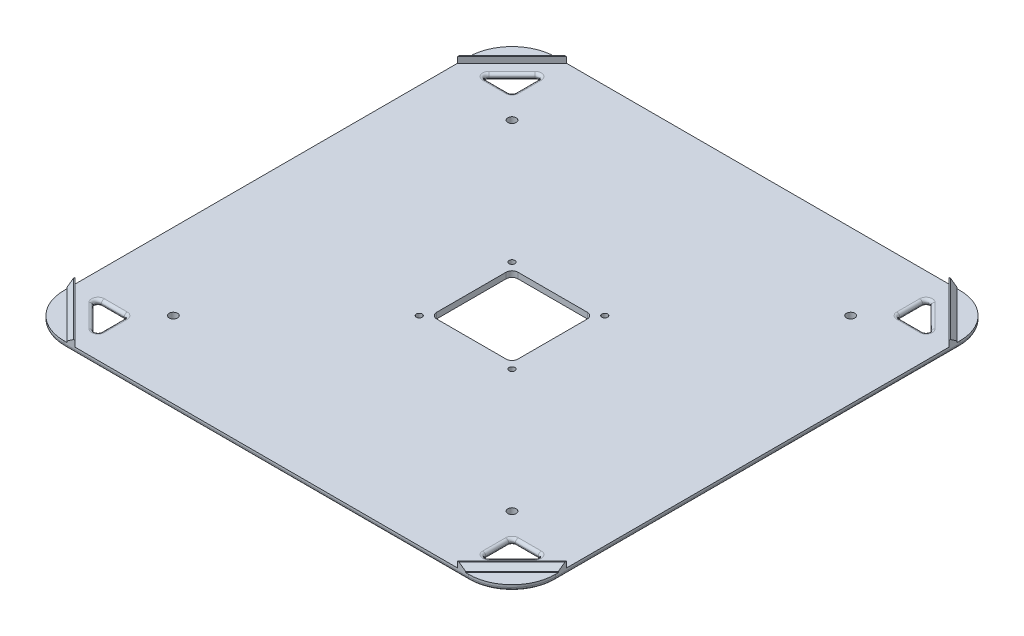
SolidWorks part; units mm, degrees
ref_plane "Front Plane" through (0, 0, 0) normal (0, 0, 1) x (1, 0, 0)
ref_plane "Top Plane" through (0, 0, 0) normal (0, 1, 0) x (1, 0, 0)
ref_plane "Right Plane" through (0, 0, 0) normal (1, 0, 0) x (0, 0, -1)
sketch "Sketch1" plane through (0, 0, 0) normal (0, 1, 0) x (1, 0, 0)
  line L5 (-134.62, -134.62) -> (134.62, -134.62)
  line L6 (-134.62, -134.62) -> (-134.62, 134.62)
  line L7 (-134.62, 134.62) -> (134.62, 134.62)
  line L8 (134.62, -134.62) -> (134.62, 134.62)
  line L9 (-134.62, -134.62) -> (134.62, 134.62) construction
  line L10 (-134.62, 134.62) -> (134.62, -134.62) construction
  point P0 (0, 0)
  dimension "D1" = 269.24
extrude "Boss-Extrude1" add sketch "Sketch1" along normal blind 3.175
fillet "Fillet1" radius 23.8125 4 edges at (134.62, 1.5875, 134.62) (134.62, 1.5875, -134.62) (-134.62, 1.5875, -134.62) (-134.62, 1.5875, 134.62)
fillet "Fillet2" radius 1.905 8 edges at (0, 0, -134.62) (127.6455, 0, -127.6455) (134.62, 0, 0) (127.6455, 0, 127.6455) (0, 0, 134.62) (-127.6455, 0, 127.6455) (-134.62, 0, 0) (-127.6455, 0, -127.6455)
sketch "Sketch9" plane through (0, 3.175, 0) normal (0, 1, 0) x (1, 0, 0)
  line L0 (134.62, -109.22) -> (109.22, -134.62)
  line L1 (109.22, -134.62) -> (104.7299, -134.62)
  line L2 (104.7299, -134.62) -> (134.62, -104.7299)
  line L3 (134.62, -104.7299) -> (134.62, -109.22)
  line L4 (-110.8075, -134.62) -> (110.8075, -134.62)
  line L5 (134.62, -110.8075) -> (134.62, 110.8075)
  line L6 (110.8075, 134.62) -> (-110.8075, 134.62)
  line L7 (-134.62, 110.8075) -> (-134.62, -110.8075)
  line L8 (-110.8075, -134.62) -> (110.8075, -134.62)
  line L9 (134.62, -110.8075) -> (134.62, 110.8075)
  line L10 (110.8075, 134.62) -> (-110.8075, 134.62)
  line L11 (-134.62, 110.8075) -> (-134.62, -110.8075)
  line L12 (-104.7299, -134.62) -> (-109.22, -134.62)
  line L13 (-109.22, -134.62) -> (-134.62, -109.22)
  line L14 (-134.62, -109.22) -> (-134.62, -104.7299)
  line L15 (-134.62, -104.7299) -> (-104.7299, -134.62)
  line L16 (-134.62, 104.7299) -> (-134.62, 109.22)
  line L17 (-134.62, 109.22) -> (-109.22, 134.62)
  line L18 (-109.22, 134.62) -> (-104.7299, 134.62)
  line L19 (-104.7299, 134.62) -> (-134.62, 104.7299)
  line L20 (104.7299, 134.62) -> (109.22, 134.62)
  line L21 (109.22, 134.62) -> (134.62, 109.22)
  line L22 (134.62, 109.22) -> (134.62, 104.7299)
  line L23 (134.62, 104.7299) -> (104.7299, 134.62)
  arc A4 (110.8075, -134.62) -> (134.62, -110.8075) centre (110.8075, -110.8075) ccw
  arc A5 (134.62, 110.8075) -> (110.8075, 134.62) centre (110.8075, 110.8075) ccw
  arc A6 (-110.8075, 134.62) -> (-134.62, 110.8075) centre (-110.8075, 110.8075) ccw
  arc A7 (-134.62, -110.8075) -> (-110.8075, -134.62) centre (-110.8075, -110.8075) ccw
  arc A8 (110.8075, -134.62) -> (134.62, -110.8075) centre (110.8075, -110.8075) ccw
  arc A9 (134.62, 110.8075) -> (110.8075, 134.62) centre (110.8075, 110.8075) ccw
  arc A10 (-110.8075, 134.62) -> (-134.62, 110.8075) centre (-110.8075, 110.8075) ccw
  arc A11 (-134.62, -110.8075) -> (-110.8075, -134.62) centre (-110.8075, -110.8075) ccw
  point P12 (134.62, 0)
  point P17 (0, -134.62)
  point P20 (0, 0)
  point P34 (0, 0)
  dimension "D2" = 25.4
  dimension "D3" = 25.4
  dimension "D4" = 3.175
  dimension "D5" = 4
  dimension "D6" = 25.4
  dimension "D7" = 25.4
  dimension "D1" = 0
extrude "Boss-Extrude2" add sketch "Sketch9" along normal blind 3.175 contours L19 L10 L17 L11 | L23 L9 L21 L10 | L13 L14 L15 L12 | L2 L3 L0 L1 region at (120.7671, 3.175, -120.7671) region at (-120.7671, 3.175, -120.7671)
sketch "Sketch8" plane through (0, 3.175, 0) normal (0, 1, 0) x (1, 0, 0)
  line L0 (-119.6749, -119.6749) -> (-92.7342, -92.7342)
  line L1 (-92.7342, 92.7342) -> (-119.6749, 119.6749)
  line L2 (119.6749, 119.6749) -> (92.7342, 92.7342)
  line L3 (92.7342, -92.7342) -> (119.6749, -119.6749)
  line L4 (-104.7299, -134.62) -> (104.7299, -134.62)
  line L5 (-104.7299, -134.62) -> (104.7299, -134.62)
  line L6 (104.7299, -134.62) -> (134.62, -104.7299)
  line L7 (104.7299, -134.62) -> (134.62, -104.7299)
  line L18 (134.62, -104.7299) -> (134.62, 104.7299)
  line L19 (134.62, -104.7299) -> (134.62, 104.7299)
  line L20 (134.62, 104.7299) -> (104.7299, 134.62)
  line L21 (134.62, 104.7299) -> (104.7299, 134.62)
  line L22 (104.7299, 134.62) -> (-104.7299, 134.62)
  line L23 (104.7299, 134.62) -> (-104.7299, 134.62)
  line L24 (-104.7299, 134.62) -> (-134.62, 104.7299)
  line L25 (-104.7299, 134.62) -> (-134.62, 104.7299)
  line L26 (-134.62, 104.7299) -> (-134.62, -104.7299)
  line L27 (-134.62, 104.7299) -> (-134.62, -104.7299)
  line L28 (-134.62, -104.7299) -> (-104.7299, -134.62)
  line L29 (-134.62, -104.7299) -> (-104.7299, -134.62)
  circle A0 centre (-92.7342, -92.7342) radius 2.286
  circle A4 centre (92.7342, -92.7342) radius 2.286
  circle A5 centre (-92.7342, 92.7342) radius 2.286
  circle A6 centre (92.7342, 92.7342) radius 2.286
  point P0 (-119.6749, -119.6749)
  point P1 (-119.6749, 119.6749)
  point P2 (-92.7342, -92.7342)
  point P4 (119.6749, 119.6749)
  point P5 (119.6749, -119.6749)
  point P7 (-92.7342, 119.6749)
  point P12 (119.6749, -92.7342)
  point P13 (119.6749, 119.6749)
  dimension "D2" = 4.572
  dimension "D3" = 90
  dimension "D4" = 38.1
  dimension "D5" = 90
  dimension "D6" = 90
  dimension "D7" = 90
  dimension "D1" = 0
extrude "Cut-Extrude4" cut sketch "Sketch8" against normal up to next contours A0 | A5 | A6 | A4
chamfer "Chamfer1" distance 2.54 4 edges at (-121.92, 6.35, 121.92) (-121.92, 6.35, -121.92) (121.92, 6.35, -121.92) (121.92, 6.35, 121.92)
sketch "Sketch10" plane through (0, 3.175, 0) normal (0, 1, 0) x (1, 0, 0)
  line L0 (-105.2108, -105.2108) -> (-124.2608, -105.2108)
  line L1 (-124.2608, -105.2108) -> (-105.2108, -124.2608)
  line L2 (-105.2108, -124.2608) -> (-105.2108, -105.2108)
  line L3 (-119.6749, -119.6749) -> (-114.7358, -114.7358)
  line L4 (-124.2608, 105.2108) -> (-105.2108, 105.2108)
  line L5 (-105.2108, 105.2108) -> (-105.2108, 124.2608)
  line L6 (-105.2108, 124.2608) -> (-124.2608, 105.2108)
  line L7 (-119.6749, 119.6749) -> (-114.7358, 114.7358)
  line L8 (-104.7299, -134.62) -> (104.7299, -134.62)
  line L9 (104.7299, -134.62) -> (134.62, -104.7299)
  line L10 (134.62, -104.7299) -> (134.62, 104.7299)
  line L11 (134.62, 104.7299) -> (104.7299, 134.62)
  line L12 (104.7299, 134.62) -> (-104.7299, 134.62)
  line L13 (-104.7299, 134.62) -> (-134.62, 104.7299)
  line L14 (-134.62, 104.7299) -> (-134.62, -104.7299)
  line L15 (-134.62, -104.7299) -> (-104.7299, -134.62)
  line L16 (-104.7299, -134.62) -> (104.7299, -134.62)
  line L17 (104.7299, -134.62) -> (134.62, -104.7299)
  line L18 (134.62, -104.7299) -> (134.62, 104.7299)
  line L19 (134.62, 104.7299) -> (104.7299, 134.62)
  line L20 (104.7299, 134.62) -> (-104.7299, 134.62)
  line L21 (-104.7299, 134.62) -> (-134.62, 104.7299)
  line L22 (-134.62, 104.7299) -> (-134.62, -104.7299)
  line L23 (-134.62, -104.7299) -> (-104.7299, -134.62)
  line L24 (105.2108, 124.2608) -> (105.2108, 105.2108)
  line L25 (105.2108, 105.2108) -> (124.2608, 105.2108)
  line L26 (124.2608, 105.2108) -> (105.2108, 124.2608)
  line L27 (119.6749, 119.6749) -> (114.7358, 114.7358)
  line L28 (124.2608, -105.2108) -> (105.2108, -105.2108)
  line L29 (105.2108, -105.2108) -> (105.2108, -124.2608)
  line L30 (105.2108, -124.2608) -> (124.2608, -105.2108)
  line L31 (119.6749, -119.6749) -> (114.7358, -114.7358)
  point P6 (-119.6749, -119.6749)
  point P10 (-114.7358, -114.7358)
  point P12 (-134.62, 0)
  point P14 (0, 134.62)
  point P19 (0, 0)
  point P24 (-119.6749, 119.6749)
  point P26 (-114.7358, 114.7358)
  point P31 (119.6749, 119.6749)
  point P33 (114.7358, 114.7358)
  point P38 (119.6749, -119.6749)
  point P40 (114.7358, -114.7358)
  point P43 (0, 0)
  dimension "D2" = 90
  dimension "D3" = 19.05
  dimension "D4" = 90
  dimension "D5" = 6.985
  dimension "D1" = 0
  dimension "D6" = 4
extrude "Cut-Extrude5" cut sketch "Sketch10" against normal up to next contours L1 L2 L0 | L5 L6 L4 | L25 L26 L24 | L29 L30 L28 region at (-111.5608, 3.175, 111.5608) region at (111.5608, 3.175, 111.5608) region at (111.5608, 3.175, -111.5608) region at (-111.5608, 3.175, -111.5608)
fillet "Fillet3" radius 1.905 12 edges at (105.2108, 1.5875, 105.2108) (124.2608, 1.5875, 105.2108) (105.2108, 1.5875, 124.2608) (105.2108, 1.5875, -124.2608) (124.2608, 1.5875, -105.2108) (105.2108, 1.5875, -105.2108) (-105.2108, 1.5875, -124.2608) (-105.2108, 1.5875, -105.2108) (-124.2608, 1.5875, -105.2108) (-105.2108, 1.5875, 105.2108) (-105.2108, 1.5875, 124.2608) (-124.2608, 1.5875, 105.2108)
fillet "Fillet4" radius 1.5875 24 edges at (-106.3868, 0, 121.4217) (-114.7358, 0, 114.7358) (-121.4217, 0, 106.3868) (-113.3888, 0, 105.2108) (-105.7688, 0, 105.7688) (-121.4217, 0, -106.3868) (-114.7358, 0, -114.7358) (-106.3868, 0, -121.4217) (-105.2108, 0, -113.3888) (-105.7688, 0, -105.7688) (105.7688, 0, -105.7688) (105.2108, 0, -113.3888) (106.3868, 0, -121.4217) (114.7358, 0, -114.7358) (121.4217, 0, -106.3868) (106.3868, 0, 121.4217) (105.2108, 0, 113.3888) (105.7688, 0, 105.7688) (113.3888, 0, 105.2108) (121.4217, 0, 106.3868) (-105.2108, 0, 113.3888) (-113.3888, 0, -105.2108) (113.3888, 0, -105.2108) (114.7358, 0, 114.7358)
fillet "Fillet5" radius 1.5875 24 edges at (105.7688, 3.175, 105.7688) (113.3888, 3.175, 105.2108) (121.4217, 3.175, 106.3868) (114.7358, 3.175, 114.7358) (106.3868, 3.175, 121.4217) (105.7688, 3.175, -105.7688) (105.2108, 3.175, -113.3888) (106.3868, 3.175, -121.4217) (114.7358, 3.175, -114.7358) (121.4217, 3.175, -106.3868) (-121.4217, 3.175, -106.3868) (-114.7358, 3.175, -114.7358) (-106.3868, 3.175, -121.4217) (-105.2108, 3.175, -113.3888) (-105.7688, 3.175, -105.7688) (-121.4217, 3.175, 106.3868) (-113.3888, 3.175, 105.2108) (-105.7688, 3.175, 105.7688) (-105.2108, 3.175, 113.3888) (-106.3868, 3.175, 121.4217) (105.2108, 3.175, 113.3888) (113.3888, 3.175, -105.2108) (-113.3888, 3.175, -105.2108) (-114.7358, 3.175, 114.7358)
sketch "Sketch11" plane through (0, 0, 0) normal (0, -1, 0) x (1, 0, 0)
  line L1 (-22.225, 22.225) -> (22.225, 22.225)
  line L2 (-22.225, 22.225) -> (-22.225, -22.225)
  line L3 (-22.225, -22.225) -> (22.225, -22.225)
  line L4 (-110.8075, -132.715) -> (110.8075, -132.715)
  line L5 (132.715, -110.8075) -> (132.715, 110.8075)
  line L6 (110.8075, 132.715) -> (-110.8075, 132.715)
  line L7 (-132.715, 110.8075) -> (-132.715, -110.8075)
  line L8 (-110.8075, -132.715) -> (110.8075, -132.715)
  line L9 (132.715, -110.8075) -> (132.715, 110.8075)
  line L10 (110.8075, 132.715) -> (-110.8075, 132.715)
  line L11 (-132.715, 110.8075) -> (-132.715, -110.8075)
  line L12 (22.225, 22.225) -> (22.225, -22.225)
  line L13 (-22.225, 22.225) -> (22.225, -22.225) construction
  line L14 (-22.225, -22.225) -> (22.225, 22.225) construction
  arc A4 (110.8075, -132.715) -> (132.715, -110.8075) centre (110.8075, -110.8075) ccw
  arc A5 (132.715, 110.8075) -> (110.8075, 132.715) centre (110.8075, 110.8075) ccw
  arc A6 (-110.8075, 132.715) -> (-132.715, 110.8075) centre (-110.8075, 110.8075) ccw
  arc A7 (-132.715, -110.8075) -> (-110.8075, -132.715) centre (-110.8075, -110.8075) ccw
  arc A8 (110.8075, -132.715) -> (132.715, -110.8075) centre (110.8075, -110.8075) ccw
  arc A9 (132.715, 110.8075) -> (110.8075, 132.715) centre (110.8075, 110.8075) ccw
  arc A10 (-110.8075, 132.715) -> (-132.715, 110.8075) centre (-110.8075, 110.8075) ccw
  arc A11 (-132.715, -110.8075) -> (-110.8075, -132.715) centre (-110.8075, -110.8075) ccw
  point P2 (0, 0)
  dimension "D2" = 44.45
  dimension "D1" = 0
extrude "Cut-Extrude6" cut sketch "Sketch11" against normal up to next contours L12 L1 L2 L3 region at (0, 0, 0)
fillet "Fillet6" radius 3.175 4 edges at (-22.225, 1.5875, -22.225) (-22.225, 1.5875, 22.225) (22.225, 1.5875, -22.225) (22.225, 1.5875, 22.225)
sketch "Sketch12" plane through (0, 0, 0) normal (0, -1, 0) x (1, 0, 0)
  line L0 (-22.225, 19.05) -> (-22.225, -19.05) construction
  line L1 (-19.05, 22.225) -> (19.05, 22.225) construction
  line L2 (22.225, 19.05) -> (22.225, -19.05) construction
  line L3 (-19.05, -22.225) -> (19.05, -22.225) construction
  line L4 (-110.8075, -132.715) -> (110.8075, -132.715)
  line L5 (132.715, -110.8075) -> (132.715, 110.8075)
  line L6 (110.8075, 132.715) -> (-110.8075, 132.715)
  line L7 (-132.715, 110.8075) -> (-132.715, -110.8075)
  line L8 (-110.8075, -132.715) -> (110.8075, -132.715)
  line L9 (132.715, -110.8075) -> (132.715, 110.8075)
  line L10 (110.8075, 132.715) -> (-110.8075, 132.715)
  line L11 (-132.715, 110.8075) -> (-132.715, -110.8075)
  line L12 (-22.225, 19.05) -> (-22.225, -19.05)
  line L13 (-19.05, 22.225) -> (19.05, 22.225)
  line L14 (22.225, 19.05) -> (22.225, -19.05)
  line L15 (-19.05, -22.225) -> (19.05, -22.225)
  line L17 (25.4, 25.4) -> (-25.4, 25.4)
  line L18 (25.4, 25.4) -> (25.4, -25.4)
  line L19 (25.4, -25.4) -> (-25.4, -25.4)
  line L20 (-25.4, 25.4) -> (-25.4, -25.4)
  line L21 (25.4, 25.4) -> (-25.4, -25.4) construction
  line L22 (25.4, -25.4) -> (-25.4, 25.4) construction
  circle A0 centre (25.4, -25.4) radius 1.5875
  circle A1 centre (-25.4, -25.4) radius 1.5875
  circle A2 centre (-25.4, 25.4) radius 1.5875
  circle A3 centre (25.4, 25.4) radius 1.5875
  arc A4 (110.8075, -132.715) -> (132.715, -110.8075) centre (110.8075, -110.8075) ccw
  arc A5 (132.715, 110.8075) -> (110.8075, 132.715) centre (110.8075, 110.8075) ccw
  arc A6 (-110.8075, 132.715) -> (-132.715, 110.8075) centre (-110.8075, 110.8075) ccw
  arc A7 (-132.715, -110.8075) -> (-110.8075, -132.715) centre (-110.8075, -110.8075) ccw
  arc A8 (110.8075, -132.715) -> (132.715, -110.8075) centre (110.8075, -110.8075) ccw
  arc A9 (132.715, 110.8075) -> (110.8075, 132.715) centre (110.8075, 110.8075) ccw
  arc A10 (-110.8075, 132.715) -> (-132.715, 110.8075) centre (-110.8075, 110.8075) ccw
  arc A11 (-132.715, -110.8075) -> (-110.8075, -132.715) centre (-110.8075, -110.8075) ccw
  point P20 (0, 0)
  dimension "D3" = 3.175
  dimension "D2" = 50.8
  dimension "D1" = 0
extrude "Cut-Extrude7" cut sketch "Sketch12" against normal up to next contours A0 | A1 | A2 | A3
